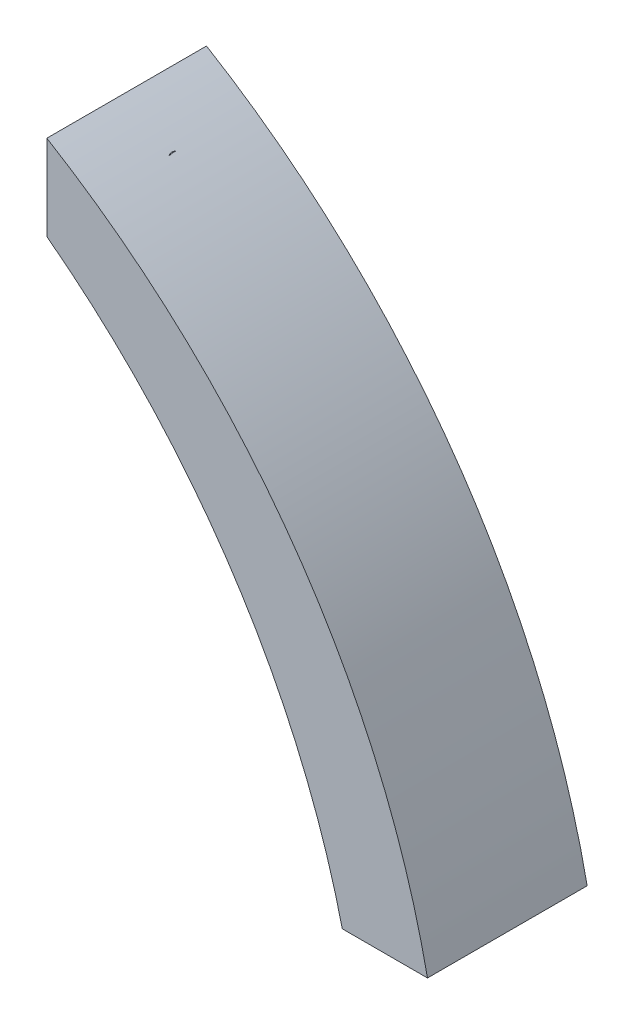
SolidWorks part; units mm, degrees
ref_plane "Front Plane" through (0, 0, 0) normal (0, 0, 1) x (1, 0, 0)
ref_plane "Top Plane" through (0, 0, 0) normal (0, 1, 0) x (1, 0, 0)
ref_plane "Right Plane" through (0, 0, 0) normal (1, 0, 0) x (0, 0, -1)
sketch "Sketch1" plane through (0, 0, 0) normal (0, 0, 1) x (1, 0, 0)
  line L0 (-19.3667, 31.4221) -> (-19.3667, 23.4221)
  line L2 (8.3902, -19.0168) -> (16.3902, -19.0168)
  arc A0 (-19.3667, 23.4221) -> (8.3902, -19.0168) centre (-64.5596, -36.4327) cw
  arc A1 (-19.3667, 31.4221) -> (16.3902, -19.0168) centre (-59.02, -34.5826) cw
  point P2 (-19.3667, 23.4221)
  point P4 (16.3902, -19.0168)
  point P6 (8.3902, -19.0168)
  dimension "D1" = 75
  dimension "D3" = 77
  dimension "D2" = 8
  dimension "D5" = 8
extrude "Boss-Extrude1" add sketch "Sketch1" along normal blind 15
sketch "Sketch4" plane through (-19.3667, 0, 0) normal (-1, 0, 0) x (0, 0, 1)
  point P0 (7.5, 27.4221)
hole_wizard "M3 Tapped Hole1" positions "3DSketch2" profile "Sketch5" tap size "M3" standard "AS"
sketch3d "3DSketch2"
  point P0 (-19.3667, 27.4221, 7.5)
cosmetic thread "Hole Thread1"
sketch "Sketch5" plane through (-19.3667, 27.4221, 7.5) normal (0, 1, 0) x (0, 0, 1)
  line L0 (0, 0) -> (0, 4.9511)
  line L1 (0, 4.9511) -> (1.25, 4.2)
  line L2 (1.25, 4.2) -> (1.25, 0.275)
  line L3 (1.25, 0.275) -> (1.525, 0)
  line L5 (1.525, 0) -> (0, 0)
  line L6 (-1.25, 0.275) -> (-1.525, 0) construction
  line L10 (0, 4.9511) -> (-1.25, 4.2) construction
  line L11 (0, -6.35) -> (0, 107.95) construction
  dimension "Tap Drill Dia." = 2.5
  dimension "Tap Drill Depth" = 4.2
  dimension "Near C'Sink Dia." = 3.05
  dimension "Near C'Sink Angle" = 90
  dimension "Drill Angle" = 118
thread "Thread1" pitch 0.5 method extrude profile "Thread Profile1" start angle 0, offset 0, length 4, pitch 0.5, diameter 2.5
ref_plane "Plane1" through (-19.0917, 27.4221, 6.25) normal (0, -1, 0) x (0, 0, -1)
sketch "Thread Profile1" plane through (-19.0917, 27.4221, 6.25) normal (0, -1, 0) x (0, 0, -1)
  line L0 (0, 0) -> (0, 0.5) construction
  line L11 (0, 0) -> (0, 0.4375)
  line L12 (0, 0.4375) -> (-0.2706, 0.2812)
  line L13 (-0.2706, 0.2812) -> (-0.2706, 0.1562)
  line L15 (-0.2706, 0.1562) -> (0, 0)
  line L17 (-0.2706, 0.2187) -> (0, 0.2187) construction
  point P2 (0, 0)
  dimension "Pitch" = 0.5
  dimension "Profile_Angle" = 60
  dimension "Profile_Land" = 0.125
  dimension "Profile_Height" = 0.2706
sketch "Sketch19" plane through (0, -19.0168, 0) normal (0, -1, 0) x (1, 0, 0)
  point P0 (12.3902, 7.5)
hole_wizard "M3 Tapped Hole2" positions "3DSketch3" profile "Sketch20" tap size "M3" standard "AS"
sketch3d "3DSketch3"
  point P0 (12.3902, -19.0168, 7.5)
sketch "Sketch20" plane through (12.3902, -19.0168, 7.5) normal (1, 0, 0) x (0, 0, -1)
  line L0 (0, 0) -> (0, 5.2511)
  line L1 (0, 5.2511) -> (1.25, 4.5)
  line L2 (1.25, 4.5) -> (1.25, 0.275)
  line L3 (1.25, 0.275) -> (1.525, 0)
  line L5 (1.525, 0) -> (0, 0)
  line L6 (-1.25, 0.275) -> (-1.525, 0) construction
  line L10 (0, 5.2511) -> (-1.25, 4.5) construction
  line L11 (0, -6.35) -> (0, 107.95) construction
  dimension "Tap Drill Dia." = 2.5
  dimension "Tap Drill Depth" = 4.5
  dimension "Near C'Sink Dia." = 3.05
  dimension "Near C'Sink Angle" = 90
  dimension "Drill Angle" = 118
cosmetic thread "Hole Thread2"
thread "Thread2" pitch 0.5 method extrude profile "Thread Profile2" start angle 0, offset 0, length 4, pitch 0.5, diameter 2.5
ref_plane "Plane2" through (13.6402, -18.7418, 7.5) normal (0, 0, 1) x (1, 0, 0)
sketch "Thread Profile2" plane through (13.6402, -18.7418, 7.5) normal (0, 0, 1) x (1, 0, 0)
  line L0 (0, 0) -> (0, 0.5) construction
  line L11 (0, 0) -> (0, 0.4375)
  line L12 (0, 0.4375) -> (-0.2706, 0.2812)
  line L13 (-0.2706, 0.2812) -> (-0.2706, 0.1562)
  line L15 (-0.2706, 0.1562) -> (0, 0)
  line L17 (-0.2706, 0.2187) -> (0, 0.2187) construction
  point P2 (0, 0)
  dimension "Pitch" = 0.5
  dimension "Profile_Angle" = 60
  dimension "Profile_Land" = 0.125
  dimension "Profile_Height" = 0.2706
equation "\"4.2.00mm\"=10"
